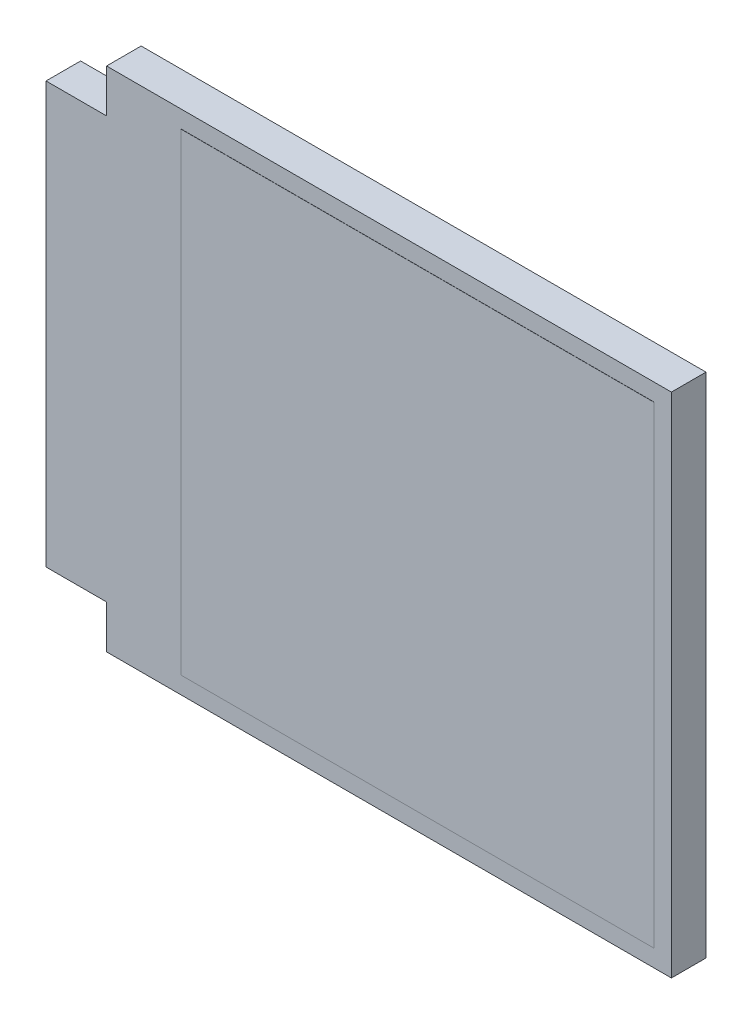
SolidWorks part; units mm, degrees
ref_plane "Plan de face" through (0, 0, 0) normal (0, 0, 1) x (1, 0, 0)
ref_plane "Plan de dessus" through (0, 0, 0) normal (0, 1, 0) x (1, 0, 0)
ref_plane "Plan de droite" through (0, 0, 0) normal (1, 0, 0) x (0, 0, -1)
sketch "Esquisse1" plane through (0, 0, 0) normal (0, 0, 1) x (1, 0, 0)
  line L0 (-48.0516, 5.41) -> (-51.5516, 5.41)
  line L1 (-48.0516, 32.25) -> (-15.3916, 32.25)
  line L2 (-48.0516, 32.25) -> (-48.0516, 2.91)
  line L3 (-48.0516, 2.91) -> (-15.3916, 2.91)
  line L4 (-15.3916, 32.25) -> (-15.3916, 2.91)
  line L5 (-51.5516, 5.41) -> (-51.5516, 29.75)
  line L6 (-51.5516, 29.75) -> (-48.0516, 29.75)
  point P6 (-49.8016, 29.75)
  point P9 (-51.5516, 17.58)
  point P10 (-48.0516, 17.58)
  dimension "D1" = 32.66
  dimension "D2" = 29.34
  dimension "D3" = 36.16
  dimension "D4" = 24.34
  dimension "D5" = 0
extrude "Boss.-Extru.1" add sketch "Esquisse1" along normal blind 2 contours L4 L1 L2 L3 | L6 L5 L0 L2 region at (-49.8016, 17.58, 0) region at (-31.7216, 17.58, 0)
sketch "Esquisse2" plane through (0, 0, 2) normal (0, 0, 1) x (1, 0, 0)
  line L0 (-48.0516, 32.25) -> (-15.3916, 32.25) construction
  line L1 (-16.3916, 31.25) -> (-43.7316, 31.25)
  line L2 (-16.3916, 31.25) -> (-16.3916, 3.91)
  line L3 (-16.3916, 3.91) -> (-43.7316, 3.91)
  line L4 (-43.7316, 31.25) -> (-43.7316, 3.91)
  line L5 (-48.0516, 2.91) -> (-15.3916, 2.91) construction
  line L6 (-48.0516, 32.25) -> (-48.0516, 29.75) construction
  line L7 (-15.3916, 32.25) -> (-15.3916, 2.91) construction
  dimension "D1" = 27.34
  dimension "D2" = 29.34
  dimension "D3" = 32.66
  dimension "D4" = 27.34
  dimension "D5" = 1
  dimension "D6" = 1
  dimension "D7" = 1
extrude "Boss.-Extru.2" add sketch "Esquisse2" along normal blind 0.01
